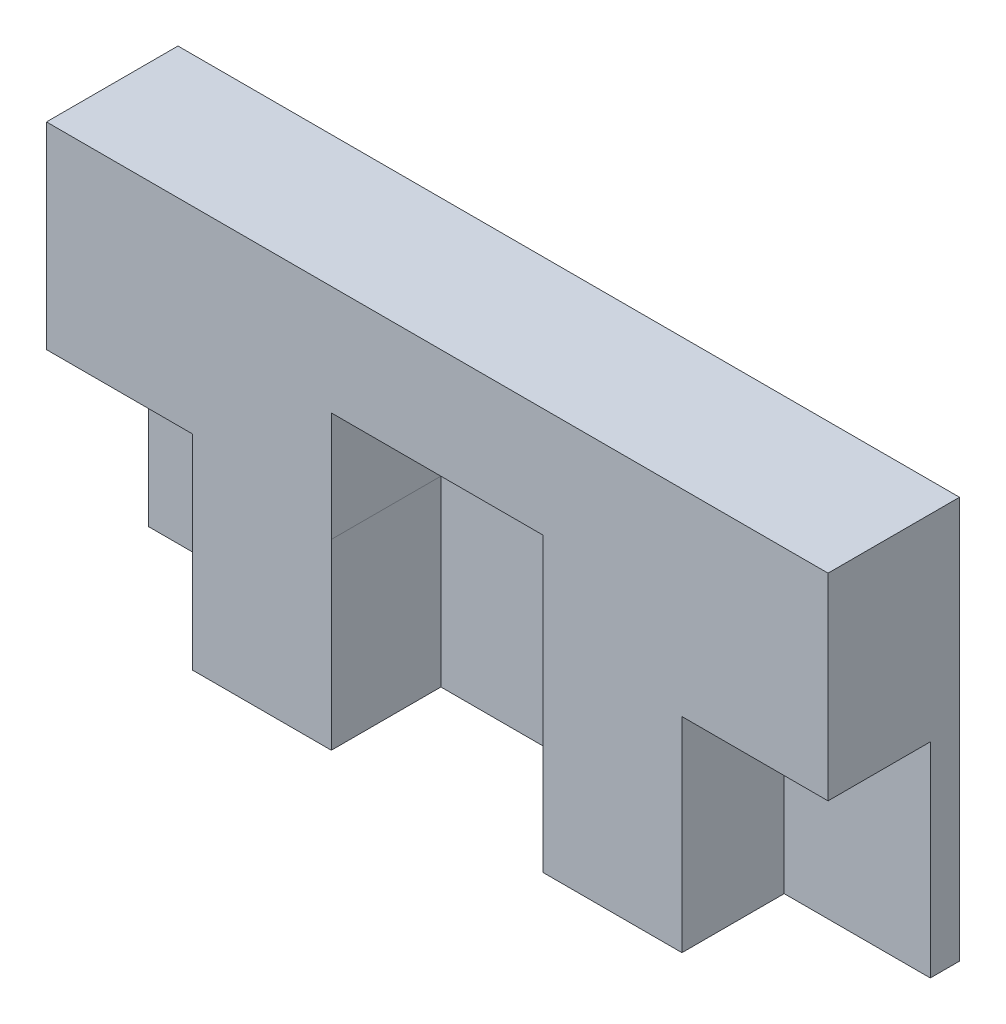
SolidWorks part; units mm, degrees
ref_plane "Front Plane" through (0, 0, 0) normal (0, 0, 1) x (1, 0, 0)
ref_plane "Top Plane" through (0, 0, 0) normal (0, 1, 0) x (1, 0, 0)
ref_plane "Right Plane" through (0, 0, 0) normal (1, 0, 0) x (0, 0, -1)
sketch "Sketch1" plane through (0, 0, 0) normal (0, 1, 0) x (1, 0, 0)
  line L1 (-339.725, 0) -> (339.725, 0)
  line L2 (-339.725, 0) -> (-339.725, 114.3)
  line L3 (-339.725, 114.3) -> (339.725, 114.3)
  line L4 (339.725, 0) -> (339.725, 114.3)
  point P5 (0, 0)
  point P6 (0, 0)
  dimension "D1" = 679.45
  dimension "D2" = 114.3
extrude "Boss-Extrude1" add sketch "Sketch1" along normal blind 349.25
sketch "Sketch2" plane through (0, 0, 0) normal (1, 0, 0) x (0, 0, -1)
  line L0 (47.625, 0) -> (47.625, 158.75)
  line L1 (0, 0) -> (114.3, 0) construction
  line L2 (0, 349.25) -> (0, 0) construction
  line L3 (0, 206.375) -> (-25.4, 206.375)
  line L4 (0, 349.25) -> (114.3, 349.25) construction
  arc A0 (47.625, 158.75) -> (0, 206.375) centre (0, 158.75) ccw
  point P8 (47.625, 181.6572)
  dimension "D1" = 47.625
  dimension "D2" = 25.4
  dimension "D3" = 142.875
sketch "Sketch4" plane through (0, 0, 0) normal (0, 1, 0) x (1, 0, 0)
  line L0 (-339.725, 0) -> (339.725, 0) construction
  line L1 (-92.075, 0) -> (92.075, 0)
  line L2 (-92.075, 0) -> (-92.075, 95.25)
  line L3 (-92.075, 95.25) -> (92.075, 95.25)
  line L4 (92.075, 0) -> (92.075, 95.25)
  point P6 (92.075, 47.625)
  point P8 (0, 95.25)
  dimension "D1" = 184.15
sweep "Cut-Sweep4" cut profiles "Sketch4" path "Sketch2"
sketch "Sketch5" plane through (0, 0, 0) normal (0, 1, 0) x (1, 0, 0)
  line L0 (0, 0) -> (0, 95.25) construction
  line L1 (-339.725, 0) -> (-212.725, 0)
  line L2 (-339.725, 0) -> (-339.725, 88.9)
  line L3 (-339.725, 88.9) -> (-212.725, 88.9)
  line L4 (-212.725, 0) -> (-212.725, 88.9)
  line L7 (339.725, 88.9) -> (212.725, 88.9)
  line L8 (339.725, 0) -> (339.725, 88.9)
  line L9 (339.725, 0) -> (212.725, 0)
  line L10 (212.725, 0) -> (212.725, 88.9)
  dimension "D1" = 127
  dimension "D2" = 88.9
extrude "Cut-Extrude1" cut sketch "Sketch5" along normal blind 177.8
